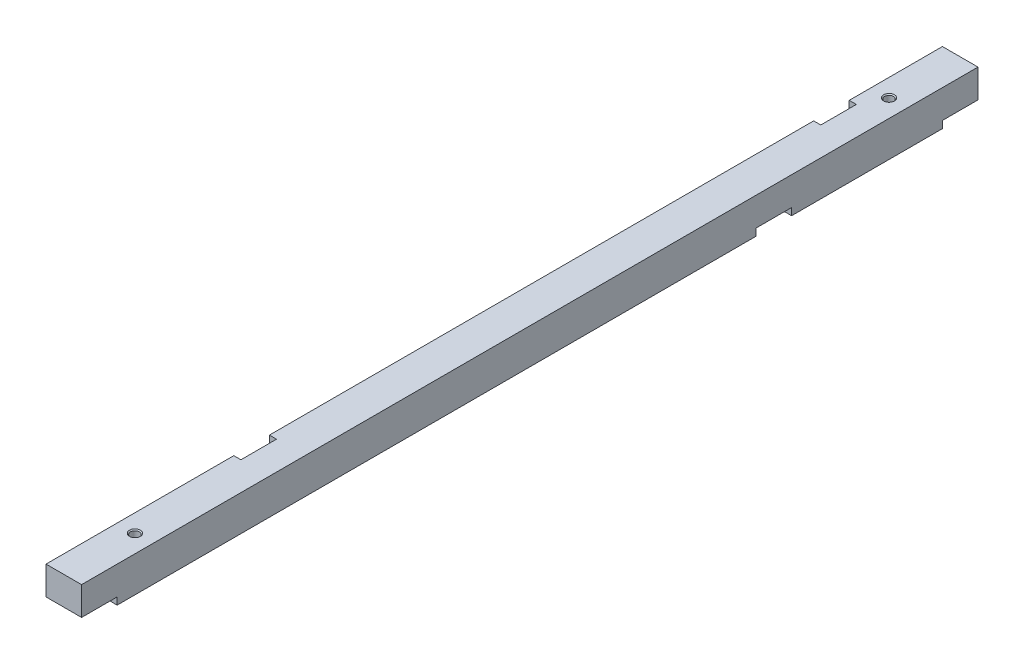
SolidWorks part; units mm, degrees
ref_plane "Plan de face" through (0, 0, 0) normal (0, 0, 1) x (1, 0, 0)
ref_plane "Plan de dessus" through (0, 0, 0) normal (0, 1, 0) x (1, 0, 0)
ref_plane "Plan de droite" through (0, 0, 0) normal (1, 0, 0) x (0, 0, -1)
sketch "Esquisse1" plane through (0, 0, 0) normal (0, 0, 1) x (1, 0, 0)
  line L0 (-5, 5) -> (5, -5) construction
  line L1 (-5, 5) -> (5, 5)
  line L2 (-5, 5) -> (-5, -5)
  line L3 (-5, -5) -> (5, -5)
  line L4 (5, 5) -> (5, -5)
  dimension "D1" = 10
extrude "Boss.-Extru.1" add sketch "Esquisse1" along normal blind 252
sketch "Esquisse2" plane through (-5, 0, 0) normal (-1, 0, 0) x (0, 0, 1)
  line L0 (0, -3) -> (0, -333) construction
  line L1 (0, -5) -> (10, -5)
  line L2 (0, -5) -> (0, -3)
  line L3 (0, -3) -> (10, -3)
  line L4 (10, -5) -> (10, -3)
  line L5 (10, -3) -> (10, -200) construction
  line L6 (52.4, -3) -> (52.4, -200) construction
  line L7 (52.4, -5) -> (62.4, -5)
  line L8 (52.4, -5) -> (52.4, -3)
  line L9 (52.4, -3) -> (62.4, -3)
  line L10 (62.4, -5) -> (62.4, -3)
  line L11 (62.4, -3) -> (62.4, -200) construction
  line L12 (242, -3) -> (242, -200) construction
  line L13 (242, -5) -> (252, -5)
  line L14 (242, -5) -> (242, -3)
  line L15 (242, -3) -> (252, -3)
  line L16 (252, -5) -> (252, -3)
  line L17 (252, -3) -> (252, -313) construction
  line L18 (252, -5) -> (0, -5) construction
  dimension "D1" = 2
extrude "Enlèv. mat.-Extru.1" cut sketch "Esquisse2" against normal through all
sketch "Esquisse3" plane through (0, -5, 0) normal (0, -1, 0) x (1, 0, 0)
  line L4 (3, 36.2) -> (3, 26.2)
  line L5 (224, 36.2) -> (3, 36.2)
  line L6 (224, 26.2) -> (224, 36.2)
  line L7 (3, 26.2) -> (224, 26.2)
  line L8 (3, 36.2) -> (3, 26.2)
  line L9 (224, 36.2) -> (3, 36.2)
  line L10 (224, 26.2) -> (224, 36.2)
  line L11 (3, 26.2) -> (224, 26.2)
  dimension "D1" = 0
extrude "Enlèv. mat.-Extru.2" [suppressed] cut sketch "Esquisse3" against normal through all
sketch "Esquisse4" plane through (0, 5, 0) normal (0, 1, 0) x (1, 0, 0)
  line L4 (3, -189.2) -> (3, -199.2)
  line L5 (3, -199.2) -> (224, -199.2)
  line L6 (224, -199.2) -> (224, -189.2)
  line L7 (224, -189.2) -> (3, -189.2)
  line L8 (3, -189.2) -> (3, -199.2)
  line L9 (3, -199.2) -> (224, -199.2)
  line L10 (224, -199.2) -> (224, -189.2)
  line L11 (224, -189.2) -> (3, -189.2)
  dimension "D1" = 0
extrude "Enlèv. mat.-Extru.3" [suppressed] cut sketch "Esquisse4" against normal through all
sketch "Esquisse5" plane through (0, 5, 0) normal (0, 1, 0) x (1, 0, 0)
  line L0 (3, -199.2) -> (224, -199.2) construction
  line L1 (-5, -199.2) -> (-3, -199.2)
  line L2 (-5, -199.2) -> (-5, -189.2)
  line L3 (-5, -189.2) -> (-3, -189.2)
  line L4 (-3, -199.2) -> (-3, -189.2)
  line L5 (3, -189.2) -> (224, -189.2) construction
  line L6 (3, -36.2) -> (224, -36.2) construction
  line L7 (-5, -36.2) -> (-3, -36.2)
  line L8 (-5, -36.2) -> (-5, -26.2)
  line L9 (-5, -26.2) -> (-3, -26.2)
  line L10 (-3, -36.2) -> (-3, -26.2)
  line L11 (3, -26.2) -> (224, -26.2) construction
  line L12 (-5, -252) -> (-5, 0) construction
  dimension "D1" = 2
extrude "Enlèv. mat.-Extru.4" cut sketch "Esquisse5" against normal through all
hole_wizard "Trou taraudé M3x0.51" positions "Esquisse7" profile "Esquisse6" tap size "M3x0.5" standard "Ansi Metric" end condition through all
sketch "Esquisse7" plane through (0, 5, 0) normal (0, 1, 0) x (1, 0, 0)
  point P0 (0, -20)
  point P3 (0, -232)
sketch "Esquisse6" plane through (0, 5, 20) normal (1, 0, 0) x (0, 0, 1)
  line L0 (0, 0) -> (0, 10)
  line L1 (0, 10) -> (1.25, 10)
  line L2 (1.25, 10) -> (1.25, 0.275)
  line L3 (1.25, 0.275) -> (1.525, 0)
  line L5 (1.525, 0) -> (0, 0)
  line L6 (-1.25, 0.275) -> (-1.525, 0) construction
  line L11 (0, -6.35) -> (0, 107.95) construction
  dimension "Diamètre du trou pour taraudage jusqu'au prochain" = 2.5
  dimension "Profondeur du trou pour taraudage jusqu'au prochain" = 10
  dimension "Diamètre du fraisage entrant" = 3.05
  dimension "Angle du fraisage entrant" = 90
cosmetic thread "Filetage de perçage1" parameters "D2"=3
cosmetic thread "Filetage de perçage2" parameters "D2"=3
